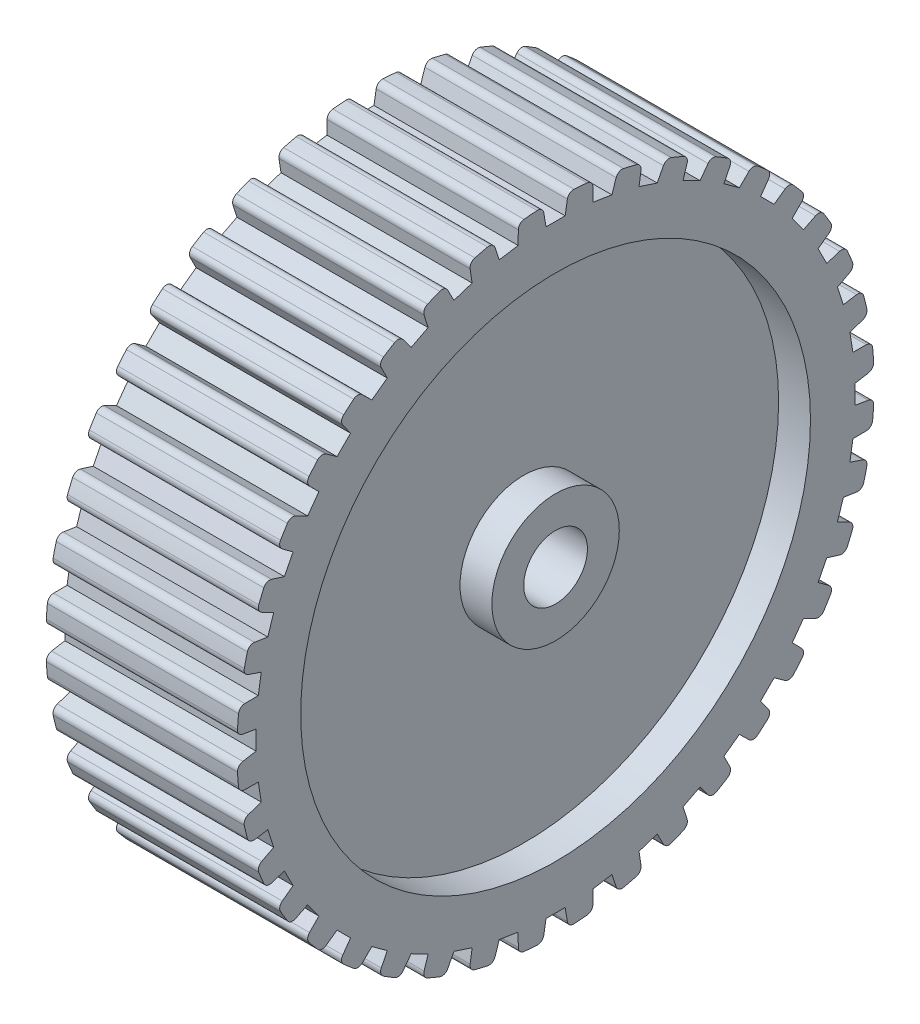
SolidWorks part; units mm, degrees
ref_plane "Front Plane" through (0, 0, 0) normal (0, 0, 1) x (1, 0, 0)
ref_plane "Top Plane" through (0, 0, 0) normal (0, 1, 0) x (1, 0, 0)
ref_plane "Right Plane" through (0, 0, 0) normal (1, 0, 0) x (0, 0, -1)
sketch "Sketch1" plane through (0, 0, 0) normal (0, 0, 1) x (1, 0, 0)
  line L0 (0, 0) -> (-52.2034, 0) construction
  line L1 (0, 5) -> (-30, 5)
  line L2 (-30, 5) -> (-30, 10)
  line L3 (-30, 10) -> (-25, 10)
  line L4 (-25, 10) -> (-25, 40)
  line L5 (-25, 40) -> (-30, 40)
  line L6 (-30, 40) -> (-30, 50)
  line L7 (-30, 50) -> (0, 50)
  line L8 (0, 50) -> (0, 40)
  line L9 (0, 40) -> (-5, 40)
  line L10 (-5, 40) -> (-5, 10)
  line L11 (-5, 10) -> (0, 10)
  line L12 (0, 10) -> (0, 5)
  dimension "D1" = 10
  dimension "D2" = 100
  dimension "D3" = 30
  dimension "D4" = 20
  dimension "D5" = 5
  dimension "D6" = 10
revolve "Revolve1" add sketch "Sketch1" angle 360 about L0
sketch "Sketch2" plane through (0, 0, 0) normal (1, 0, 0) x (0, 0, -1)
  line L0 (-2.5, 53) -> (-1.5, 47)
  line L1 (-1.5, 47) -> (1.5, 47)
  line L2 (1.5, 47) -> (2.5, 53)
  line L3 (2.5, 53) -> (-2.5, 53)
  circle A0 centre (0, 0) radius 50 construction
  point P3 (0, 47)
  point P6 (0, 53)
  point P7 (0, 50)
  dimension "D1" = 3
  dimension "D2" = 5
  dimension "D3" = 6
  dimension "D4" = 3
extrude "Cut-Extrude1" cut sketch "Sketch2" against normal blind 44
fillet "Fillet1" radius 1 2 edges at (-15, 49.9602, 1.9934) (-15, 49.9602, -1.9934)
pattern_circular "CirPattern1" count 40 over 360 about axis through (0, 0, 0) along (1, 0, 0) of "Cut-Extrude1", "Fillet1"
scale "Scale1" bodies to scale 103 scale about centroid uniform scaling yes scale factor 0.5
